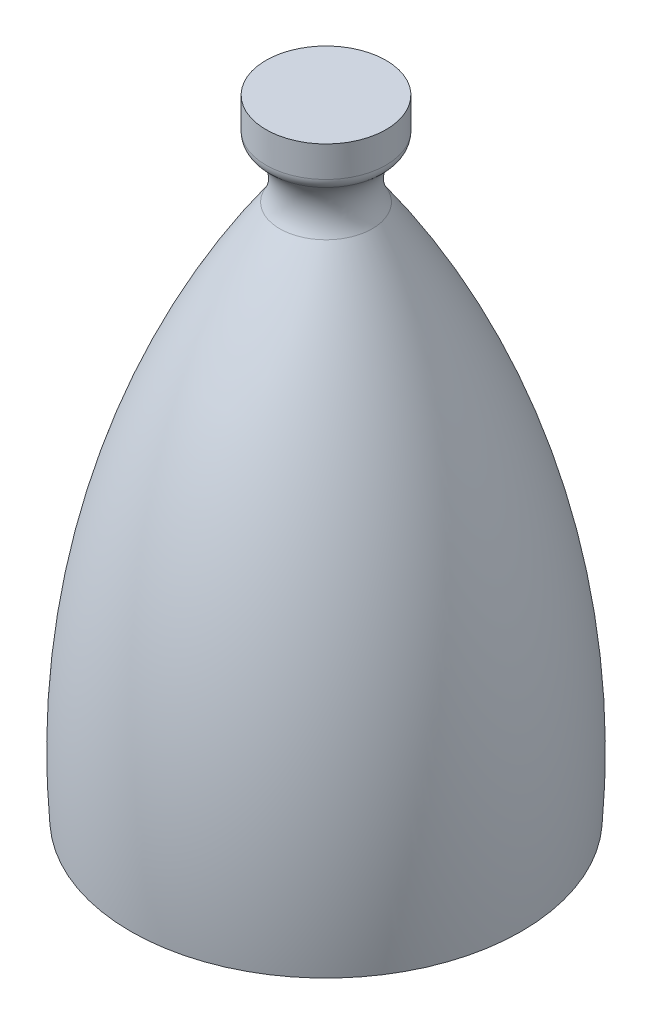
SolidWorks part; units mm, degrees
ref_plane "Front Plane" through (0, 0, 0) normal (0, 0, 1) x (1, 0, 0)
ref_plane "Top Plane" through (0, 0, 0) normal (0, 1, 0) x (1, 0, 0)
ref_plane "Right Plane" through (0, 0, 0) normal (1, 0, 0) x (0, 0, -1)
sketch "Sketch7" plane through (0, 0, 0) normal (0, 0, 1) x (1, 0, 0)
  line L0 (71.7029, 564.084) -> (216.4029, 564.084)
  line L1 (71.7029, 564.084) -> (71.7029, 1028.28)
  line L2 (116.1747, 1000.3538) -> (71.7029, 1000.3538)
  line L3 (71.7029, 1028.28) -> (116.1747, 1028.28)
  line L4 (116.1747, 1028.28) -> (116.1747, 1000.3538)
  line L5 (71.7029, 564.084) -> (71.7029, 1073.7458) construction
  arc A0 (216.4029, 564.084) -> (105.9827, 959.5858) centre (-389.9251, 607.9682) ccw
  arc A1 (105.9827, 959.5858) -> (116.1747, 1000.3538) centre (131.4627, 974.8738) cw
  dimension "D1" = 144.7
  dimension "D2" = 464.196
revolve "Revolve1" add sketch "Sketch7" angle 360 about L5 region at (132.3115, 738.1131, 0)
revolve "Revolve2" add sketch "Sketch7<4>" angle 360 about L5 region at (93.9388, 1014.3169, 0)
sketch "Sketch7<4>" plane through (0, 0, 0) normal (0, 0, 1) x (1, 0, 0) same geometry as "Sketch7"
fillet "Fillet1" radius 10 1 edges at (71.7029, 1000.3538, -44.4718)
